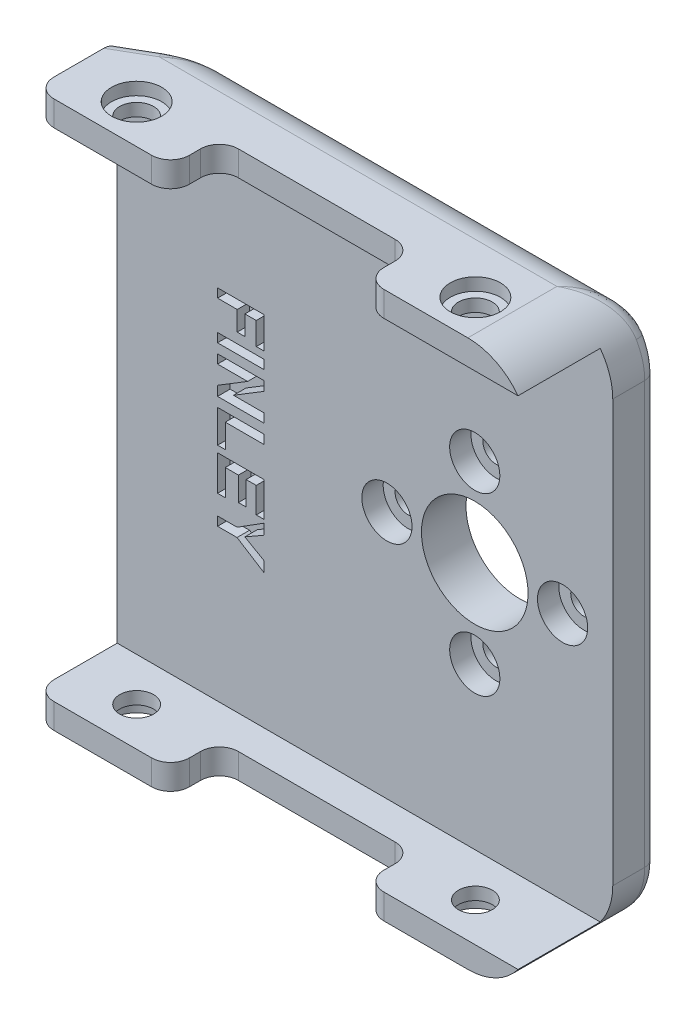
SolidWorks part; units mm, degrees
note: '?' marks a value the reader was unsure of.
material "Esun Hard Tough Resin"
ref_plane "Plan de face" through (0, 0, 0) normal (0, 0, 1) x (1, 0, 0)
ref_plane "Plan de dessus" through (0, 0, 0) normal (0, 1, 0) x (1, 0, 0)
ref_plane "Plan de droite" through (0, 0, 0) normal (1, 0, 0) x (0, 0, -1)
ref_axis "hip_z_rotation_axis" through (0, 0, -22.6557) along (0, 0, 1)?
sketch "Sketch1" plane through (0, 0, 0) normal (0, 0, 1) x (1, 0, 0)
  line L0 (0, 0) -> (8, 0) construction
  line L1 (0, 0) -> (-6.9282, -4) construction
  line L2 (0, 0) -> (-6.9282, 4) construction
  line L3 (-6.9282, -4) -> (-6.9282, 4) construction
  circle A0 centre (0, 0) radius 8 construction
  circle A1 centre (5.6569, -5.6569) radius 1
  circle A2 centre (0, -8) radius 1
  circle A3 centre (8, 0) radius 1
  circle A4 centre (-5.6569, -5.6569) radius 1
  circle A5 centre (-8, 0) radius 1
  circle A6 centre (-5.6569, 5.6569) radius 1
  circle A7 centre (0, 8) radius 1
  circle A8 centre (5.6569, 5.6569) radius 1
  circle A9 centre (0, 0) radius 4
  point P31 (0, 0)
  dimension "D1" = 16
  dimension "D2" = 2
  dimension "D5" = 8
  dimension "D3" = 60
  dimension "D4" = 8
sketch "Sketch3" plane through (0, 0, 0) normal (0, 1, 0) x (1, 0, 0)
  circle A0 centre (4, -6.7) radius 1.3
  circle A1 centre (-18, -6.7) radius 1.3
  dimension "D1" = 2.6
  dimension "D2" = 2.6
  dimension "D3" = 18
  dimension "D5" = 6.7
  dimension "D4" = 4
sketch "Sketch4" plane through (0, 0, 0) normal (0, 0, 1) x (1, 0, 0)
  line L0 (-28.5, 0) -> (11, 0) construction
  line L1 (-28.5, 21.8) -> (11, 21.8)
  line L2 (-28.5, 21.8) -> (-28.5, -21.8)
  line L3 (-28.5, -21.8) -> (11, -21.8)
  line L4 (11, 21.8) -> (11, -21.8)
  circle A0 centre (0, 0) radius 11 construction
  dimension "D4" = 22
  dimension "D1" = 28.5
  dimension "D2" = 43.6
  dimension "D3" = 11
extrude "Boss-Extrude1" add sketch "Sketch4" along normal blind 10.1
sketch "Sketch5" plane through (11, 0, 0) normal (1, 0, 0) x (0, 0, -1)
  line L0 (-10.1, -21.8) -> (-10.1, 21.8) construction
  line L1 (-10.1, 19.8) -> (-3.55, 19.8)
  line L2 (-10.1, 19.8) -> (-10.1, -19.8)
  line L3 (-10.1, -19.8) -> (-3.55, -19.8)
  line L4 (-3.55, 19.8) -> (-3.55, -19.8)
  line L6 (-10.1, 21.8) -> (0, 21.8) construction
  line L7 (-10.1, -21.8) -> (0, -21.8) construction
  dimension "D1" = 6.55
  dimension "D2" = 2
  dimension "D3" = 2
extrude "Cut-Extrude1" cut sketch "Sketch5" against normal through all
sketch "Sketch17" plane through (0, 0, 0) normal (0, 0, -1) x (-1, 0, 0)
  circle A0 centre (0, 0) radius 4.25
  dimension "D1" = 8.5
extrude "Cut-Extrude5" cut sketch "Sketch17" against normal through all
sketch "Sketch12" plane through (0, 0, 3.55) normal (0, 0, 1) x (1, 0, 0)
  circle A0 centre (0, 0) radius 4.15
  circle A1 centre (0, 0) radius 4 construction
  dimension "D1" = 0.15
extrude "Cut-Extrude2" [suppressed] cut sketch "Sketch12" against normal up to next contours A0
sketch "Sketch13" plane through (0, 0, 3.55) normal (0, 0, 1) x (1, 0, 0)
  line L0 (0, 0) -> (8, 0) construction
  line L1 (0, 0) -> (-6.9282, 4) construction
  line L2 (0, 0) -> (-6.9282, -4) construction
  circle A0 centre (0, 0) radius 5 construction
  circle A1 centre (-4.3301, 2.5) radius 0.375
  circle A2 centre (-4.3301, -2.5) radius 0.375
  circle A3 centre (5, 0) radius 0.375
  circle A4 centre (0, 0) radius 4 construction
  dimension "D1" = 0.75
  dimension "D2" = 1
extrude "Cut-Extrude3" [suppressed] cut sketch "Sketch13" against normal blind 1
sketch "Sketch14" plane through (0, 0, 3.55) normal (0, 0, 1) x (1, 0, 0)
  line L0 (-28.5, -19.8) -> (-28.5, 19.8) construction
  line L1 (-28.5, 10.25) -> (11, 10.25)
  line L2 (-28.5, 10.25) -> (-28.5, 12.25)
  line L3 (-28.5, 12.25) -> (11, 12.25)
  line L4 (11, 10.25) -> (11, 12.25)
  line L5 (11, -19.8) -> (11, 19.8) construction
  line L6 (0, 0) -> (-23.2886, 0) construction
  line L7 (-28.5, -12.25) -> (11, -12.25)
  line L8 (-28.5, -12.25) -> (-28.5, -10.25)
  line L9 (-28.5, -10.25) -> (11, -10.25)
  line L10 (11, -12.25) -> (11, -10.25)
  dimension "D3" = 12.25
  dimension "D4" = 2
hole_wizard "CBORE for M2 Hex Socket Head Cap Screw1" [suppressed] positions "Sketch11" profile "Sketch10" counterbore size "M2" standard "ISO"
sketch "Sketch11" plane through (0, 0, 4) normal (0, 0, 1) x (1, 0, 0)
  point P0 (-5.6569, 5.6569)
  point P3 (-8, 0)
  point P6 (-5.6569, -5.6569)
  point P9 (0, -8)
  point P12 (5.6569, -5.6569)
  point P15 (8, 0)
  point P18 (5.6569, 5.6569)
  point P21 (0, 8)
sketch "Sketch10" plane through (-5.6569, 5.6569, 4) normal (1, 0, 0) x (0, -1, 0)
  line L0 (0, 0) -> (0, 4)
  line L1 (0, 4) -> (1.1, 4)
  line L2 (1.1, 2.725) -> (1.1, 4)
  line L3 (1.1, 2.725) -> (1.125, 2.7)
  line L4 (1.125, 2.7) -> (2.2, 2.7)
  line L5 (2.2, 2.7) -> (2.2, 0)
  line L7 (0, 0) -> (2.2, 0)
  line L9 (-1.1, 2.725) -> (-1.125, 2.7) construction
  line L11 (0, -6.35) -> (0, 107.95) construction
  dimension "Thru Hole Dia." = 2.2
  dimension "Thru Hole Depth" = 4
  dimension "C'Bore Dia." = 4.4
  dimension "C'Bore Depth" = 2.7
  dimension "Mid C'Sink Dia." = 2.25
  dimension "Mid C'Sink Angle" = 90
sketch "Sketch18" plane through (0, 0, 3.55) normal (0, 0, 1) x (1, 0, 0)
  circle A0 centre (0, 0) radius 7 construction
  circle A1 centre (0, 7) radius 1.05
  dimension "D1" = 14
  dimension "D2" = 2.1
extrude "Cut-Extrude6" cut sketch "Sketch18" against normal through all
sketch "Sketch19" plane through (0, 0, 3.55) normal (0, 0, 1) x (1, 0, 0)
  circle A0 centre (0, 7) radius 2
  dimension "D1" = 4
extrude "Cut-Extrude7" cut sketch "Sketch19" against normal blind 1.7
pattern_circular "CirPattern1" count 4 over 360 about axis through (0, 0, 0) along (0, 0, 1) of "Cut-Extrude7", "Cut-Extrude6"
sketch "Sketch20" plane through (0, 21.8, 0) normal (0, 1, 0) x (1, 0, 0)
  line L0 (-28.5, -10.1) -> (-28.5, 0) construction
  line L3 (11, -10.1) -> (-28.5, -10.1) construction
  line L4 (-17.7, -10.1) -> (-2.2, -10.1)
  line L5 (-17.7, -10.1) -> (-17.7, -6.2)
  line L6 (-17.7, -6.2) -> (-2.2, -6.2)
  line L7 (-2.2, -10.1) -> (-2.2, -6.2)
  circle A0 centre (-23.5, -7) radius 1.35
  circle A1 centre (3.5, -7) radius 1.35
  dimension "D1" = 2.7
  dimension "D2" = 2.7
  dimension "D3" = 27
  dimension "D4" = 5
  dimension "D5" = 3.1
  dimension "D6" = 15.5
  dimension "D7" = 3.9
  dimension "D8" = 10.8
extrude "Cut-Extrude8" cut sketch "Sketch20" against normal through all
chamfer "Chamfer1" [suppressed] distance 0.5 angle 45
chamfer "Chamfer3" distance 6 angle 30 1 edges at (-28.5, 0, 0) first distance on face at (7, -1.05, 0)
fillet "Fillet1" radius 3 2 edges at (-5.75, 21.8, 0) (-5.75, -21.8, 0)
fillet "Fillet5" radius 5 2 edges at (11, 21.8, 6.55) (11, -21.8, 6.55) tangent propagation no
fillet "Fillet9" radius 1 10 edges at (9.0748, -20.7428, 0.7141) (10.8945, -17.8215, 0) (11, 0, 0) (10.8945, 17.8215, 0) (9.0748, 20.7428, 0.7141) (-28.0981, 21.8, 3.2321) (-28.0981, -21.8, 3.2321) (-24.0219, 20.9213, 0.8787) (-24.0219, -20.9213, 0.8787) (-22.5, 0, 0)
sketch "Sketch16" plane through (0, 0, 3.55) normal (0, 0, 1) x (1, 0, 0)
  line L0 (-20.5, 9.25) -> (-20.5, -9.25) construction
  line L2 (-20.5, 0) -> (0, 0) construction
  line L3 (-28.5, -19.8) -> (-28.5, 19.8) construction
  text T0 "FINLEY" font "Arial" height 3.7
  dimension "D1" = 18.5
  dimension "D2" = 8
extrude "Poppy_trademark" cut sketch "Sketch16" against normal blind 1
fillet "Fillet11" radius 1.5 10 edges at (-17.7, -20.8, 6.2) (-17.7, -20.8, 10.1) (-2.2, -20.8, 6.2) (-2.2, -20.8, 10.1) (-28.5, -20.8, 10.1) (-28.5, 20.8, 10.1) (-2.2, 20.8, 10.1) (-2.2, 20.8, 6.2) (-17.7, 20.8, 6.2) (-17.7, 20.8, 10.1)
sketch "Sketch21" plane through (0, 21.8, 0) normal (0, 1, 0) x (1, 0, 0)
  circle A0 centre (-23.5, -7) radius 2
  circle A1 centre (3.5, -7) radius 2
  dimension "D1" = 4
extrude "Cut-Extrude9" cut sketch "Sketch21" against normal blind 1
mirror "Mirror1" about plane through (0, 0, 0) normal (0, 1, 0) of "Cut-Extrude9"
equation "\"Tolerance\"=0.15"
equation "\"D1@Sketch12\"=\"Tolerance\""
equation "\"Tickness\"= 4mm"
equation "\"C'Bore Depth@Sketch10\"=\"Tickness\" - \"M2_counterbore_thickness\""
equation "\"M2_counterbore_thickness\"= 1.3"
